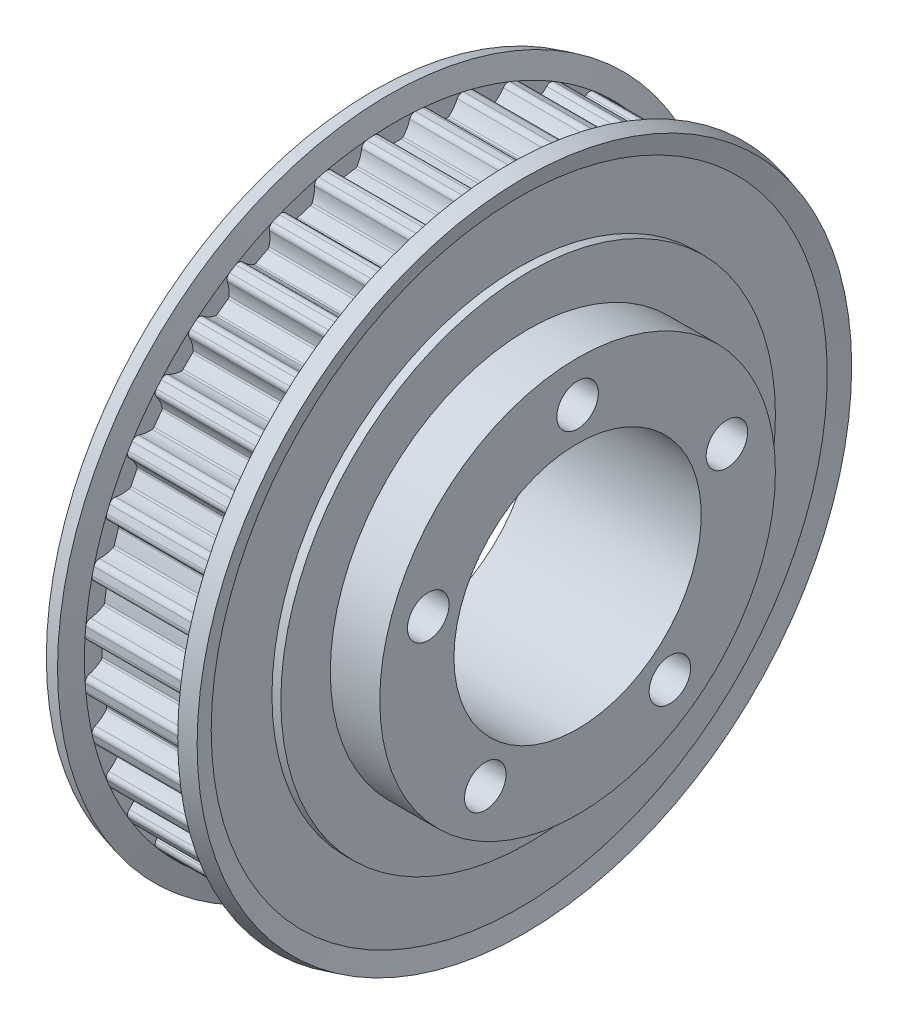
SolidWorks part; units mm, degrees
ref_plane "Front Plane" through (0, 0, 0) normal (0, 0, 1) x (1, 0, 0)
ref_plane "Top Plane" through (0, 0, 0) normal (0, 1, 0) x (1, 0, 0)
ref_plane "Right Plane" through (0, 0, 0) normal (1, 0, 0) x (0, 0, -1)
ref_plane "Plane1" through (0, 0, 0) normal (0, 0, 1) x (1, 0, 0)
sketch "Sketch1" plane through (0, 0, 0) normal (0, 0, 1) x (1, 0, 0)
  line L0 (0, 0) -> (0, 25)
  line L1 (0, 25) -> (0.9, 25)
  line L2 (0.9, 25) -> (0.9, 31.1394)
  line L3 (0.9, 31.1394) -> (0.3784, 33.0859)
  line L4 (0.3784, 33.0859) -> (1.9239, 33.5)
  line L5 (1.9239, 33.5) -> (2.5, 31.35)
  line L6 (2.5, 31.35) -> (13.5, 31.35)
  line L7 (13.5, 31.35) -> (14.0761, 33.5)
  line L8 (14.0761, 33.5) -> (15.6216, 33.0859)
  line L9 (15.6216, 33.0859) -> (15.1, 31.1394)
  line L10 (15.1, 31.1394) -> (15.1, 25)
  line L11 (15.1, 25) -> (16, 25)
  line L12 (16, 25) -> (16, 23.5)
  line L13 (16, 23.5) -> (21, 23.5)
  line L14 (21, 23.5) -> (21, 0)
  line L15 (21, 0) -> (0, 0)
  line L16 (21, 0) -> (0, 0) construction
revolve "Revolve1" add sketch "Sketch1" angle 360 about L16 reverse direction yes
ref_plane "Plane2" through (0, 0, 0) normal (0, 0, 1) x (1, 0, 0)
sketch "Sketch2" plane through (0, 0, 0) normal (0, 0, 1) x (1, 0, 0)
  line L0 (0, 0) -> (0, 12.5)
  line L1 (0, 12.5) -> (21, 12.5)
  line L2 (21, 12.5) -> (21, 0)
  line L3 (21, 0) -> (0, 0)
  line L4 (21, 0) -> (0, 0) construction
revolve "Cut-Revolve1" cut sketch "Sketch2" angle 360 about L4 reverse direction yes
ref_plane "Plane3" through (2.5, 0, 0) normal (1, 0, 0) x (0, 0, -1)
sketch "Sketch3" plane through (2.5, 0, 0) normal (1, 0, 0) x (0, 0, -1)
  line L0 (2.0877, 31.2804) -> (2.0877, 31.7615)
  line L1 (-2.0877, 31.7615) -> (-2.0877, 31.2804)
  arc A0 (-2.0877, 31.2804) -> (-1.5225, 30.8836) centre (-2.0511, 30.7316) cw
  arc A1 (-1.5225, 30.8836) -> (-0.8639, 29.6599) centre (1.625, 31.7885) ccw
  arc A2 (-0.8639, 29.6599) -> (-0.6683, 29.5725) centre (-0.6739, 29.8224) ccw
  arc A3 (-0.6683, 29.5725) -> (0.6683, 29.5725) centre (0, 0) cw
  arc A4 (0.6683, 29.5725) -> (0.8639, 29.6599) centre (0.6739, 29.8224) ccw
  arc A5 (0.8639, 29.6599) -> (1.5225, 30.8836) centre (-1.625, 31.7885) ccw
  arc A6 (1.5225, 30.8836) -> (2.0877, 31.2804) centre (2.0511, 30.7316) cw
  arc A7 (2.0877, 31.7615) -> (-2.0877, 31.7615) centre (0, 0) ccw
extrude "Cut-Extrude1" cut sketch "Sketch3" along normal blind 11
ref_plane "Plane4" through (2.5, 0, 0) normal (1, 0, 0) x (0, 0, -1)
sketch "Sketch4" plane through (2.5, 0, 0) normal (1, 0, 0) x (0, 0, -1)
  line L0 (6.9554, 30.5687) -> (7.0306, 31.0438)
  line L1 (2.9066, 31.697) -> (2.8313, 31.2219)
  arc A0 (2.8313, 31.2219) -> (3.3275, 30.7415) centre (2.7816, 30.6741) cw
  arc A1 (3.3275, 30.7415) -> (3.7865, 29.4299) centre (6.5778, 31.1429) ccw
  arc A2 (3.7865, 29.4299) -> (3.9661, 29.3129) centre (3.9996, 29.5606) ccw
  arc A3 (3.9661, 29.3129) -> (5.2862, 29.1038) centre (0, 0) cw
  arc A4 (5.2862, 29.1038) -> (5.4931, 29.1596) centre (5.3309, 29.3498) ccw
  arc A5 (5.4931, 29.1596) -> (6.335, 30.2652) centre (3.3678, 31.6513) ccw
  arc A6 (6.335, 30.2652) -> (6.9554, 30.5687) centre (6.8333, 30.0324) cw
  arc A7 (7.0306, 31.0438) -> (2.9066, 31.697) centre (0, 0) ccw
extrude "Cut-Extrude2" cut sketch "Sketch4" along normal blind 11
ref_plane "Plane5" through (2.5, 0, 0) normal (1, 0, 0) x (0, 0, -1)
sketch "Sketch5" plane through (2.5, 0, 0) normal (1, 0, 0) x (0, 0, -1)
  line L0 (11.6517, 29.1043) -> (11.8004, 29.5618)
  line L1 (7.8293, 30.8521) -> (7.6806, 30.3946)
  arc A0 (7.6806, 30.3946) -> (8.0956, 29.8425) centre (7.5459, 29.8613) cw
  arc A1 (8.0956, 29.8425) -> (8.3438, 28.4752) centre (11.3687, 29.7305) ccw
  arc A2 (8.3438, 28.4752) -> (8.5028, 28.3316) centre (8.5747, 28.571) ccw
  arc A3 (8.5028, 28.3316) -> (9.774, 27.9186) centre (0, 0) cw
  arc A4 (9.774, 27.9186) -> (9.987, 27.9413) centre (9.8566, 28.1545) ccw
  arc A5 (9.987, 27.9413) -> (10.9915, 28.9016) centre (8.2777, 30.7348) ccw
  arc A6 (10.9915, 28.9016) -> (11.6517, 29.1043) centre (11.4473, 28.5937) cw
  arc A7 (11.8004, 29.5618) -> (7.8293, 30.8521) centre (0, 0) ccw
extrude "Cut-Extrude3" cut sketch "Sketch5" along normal blind 11
ref_plane "Plane6" through (2.5, 0, 0) normal (1, 0, 0) x (0, 0, -1)
sketch "Sketch6" plane through (2.5, 0, 0) normal (1, 0, 0) x (0, 0, -1)
  line L0 (16.0612, 26.9232) -> (16.2796, 27.3519)
  line L1 (12.5592, 29.2475) -> (12.3408, 28.8189)
  arc A0 (12.3408, 28.8189) -> (12.6643, 28.2087) centre (12.1243, 28.3133) cw
  arc A1 (12.6643, 28.2087) -> (12.6956, 26.8194) centre (15.8796, 27.586) ccw
  arc A2 (12.6956, 26.8194) -> (12.8302, 26.6526) centre (12.9386, 26.8779) ccw
  arc A3 (12.8302, 26.6526) -> (14.021, 26.0459) centre (0, 0) cw
  arc A4 (14.021, 26.0459) -> (14.2351, 26.035) centre (14.1396, 26.266) ccw
  arc A5 (14.2351, 26.035) -> (15.3774, 26.8263) centre (12.9838, 29.0615) ccw
  arc A6 (15.3774, 26.8263) -> (16.0612, 26.9232) centre (15.7794, 26.4509) cw
  arc A7 (16.2796, 27.3519) -> (12.5592, 29.2475) centre (0, 0) ccw
extrude "Cut-Extrude4" cut sketch "Sketch6" along normal blind 11
ref_plane "Plane7" through (2.5, 0, 0) normal (1, 0, 0) x (0, 0, -1)
sketch "Sketch7" plane through (2.5, 0, 0) normal (1, 0, 0) x (0, 0, -1)
  line L0 (20.0752, 24.0793) -> (20.3579, 24.4684)
  line L1 (16.9799, 26.9227) -> (16.6972, 26.5335)
  arc A0 (16.6972, 26.5335) -> (16.9212, 25.8803) centre (16.4042, 26.068) cw
  arc A1 (16.9212, 25.8803) -> (16.7347, 24.5032) centre (19.9995, 24.7623) ccw
  arc A2 (16.7347, 24.5032) -> (16.8416, 24.3174) centre (16.9839, 24.5229) ccw
  arc A3 (16.8416, 24.3174) -> (17.9229, 23.5318) centre (0, 0) cw
  arc A4 (17.9229, 23.5318) -> (18.1326, 23.4876) centre (18.0744, 23.7307) ccw
  arc A5 (18.1326, 23.4876) -> (19.3847, 24.0904) centre (17.3702, 26.6726) ccw
  arc A6 (19.3847, 24.0904) -> (20.0752, 24.0793) centre (19.723, 23.6568) cw
  arc A7 (20.3579, 24.4684) -> (16.9799, 26.9227) centre (0, 0) ccw
extrude "Cut-Extrude5" cut sketch "Sketch7" along normal blind 11
ref_plane "Plane8" through (2.5, 0, 0) normal (1, 0, 0) x (0, 0, -1)
sketch "Sketch8" plane through (2.5, 0, 0) normal (1, 0, 0) x (0, 0, -1)
  line L0 (23.5948, 20.6423) -> (23.935, 20.9825)
  line L1 (20.9825, 23.935) -> (20.6423, 23.5948)
  arc A0 (20.6423, 23.5948) -> (20.7614, 22.9146) centre (20.2802, 23.1809) cw
  arc A1 (20.7614, 22.9146) -> (20.3618, 21.5836) centre (23.6269, 21.3288) ccw
  arc A2 (20.3618, 21.5836) -> (20.4383, 21.3834) centre (20.6111, 21.5641) ccw
  arc A3 (20.4383, 21.3834) -> (21.3834, 20.4383) centre (0, 0) cw
  arc A4 (21.3834, 20.4383) -> (21.5836, 20.3618) centre (21.5641, 20.6111) ccw
  arc A5 (21.5836, 20.3618) -> (22.9146, 20.7614) centre (21.3288, 23.6269) ccw
  arc A6 (22.9146, 20.7614) -> (23.5948, 20.6423) centre (23.1809, 20.2802) cw
  arc A7 (23.935, 20.9825) -> (20.9825, 23.935) centre (0, 0) ccw
extrude "Cut-Extrude6" cut sketch "Sketch8" along normal blind 11
ref_plane "Plane9" through (2.5, 0, 0) normal (1, 0, 0) x (0, 0, -1)
sketch "Sketch9" plane through (2.5, 0, 0) normal (1, 0, 0) x (0, 0, -1)
  line L0 (26.5335, 16.6972) -> (26.9227, 16.9799)
  line L1 (24.4684, 20.3579) -> (24.0793, 20.0752)
  arc A0 (24.0793, 20.0752) -> (24.0904, 19.3847) centre (23.6568, 19.723) cw
  arc A1 (24.0904, 19.3847) -> (23.4876, 18.1326) centre (26.6726, 17.3702) ccw
  arc A2 (23.4876, 18.1326) -> (23.5318, 17.9229) centre (23.7307, 18.0744) ccw
  arc A3 (23.5318, 17.9229) -> (24.3174, 16.8416) centre (0, 0) cw
  arc A4 (24.3174, 16.8416) -> (24.5032, 16.7347) centre (24.5229, 16.9839) ccw
  arc A5 (24.5032, 16.7347) -> (25.8803, 16.9212) centre (24.7623, 19.9995) ccw
  arc A6 (25.8803, 16.9212) -> (26.5335, 16.6972) centre (26.068, 16.4042) cw
  arc A7 (26.9227, 16.9799) -> (24.4684, 20.3579) centre (0, 0) ccw
extrude "Cut-Extrude7" cut sketch "Sketch9" along normal blind 11
ref_plane "Plane10" through (2.5, 0, 0) normal (1, 0, 0) x (0, 0, -1)
sketch "Sketch10" plane through (2.5, 0, 0) normal (1, 0, 0) x (0, 0, -1)
  line L0 (28.8189, 12.3408) -> (29.2475, 12.5592)
  line L1 (27.3519, 16.2796) -> (26.9232, 16.0612)
  arc A0 (26.9232, 16.0612) -> (26.8263, 15.3774) centre (26.4509, 15.7794) cw
  arc A1 (26.8263, 15.3774) -> (26.035, 14.2351) centre (29.0615, 12.9838) ccw
  arc A2 (26.035, 14.2351) -> (26.0459, 14.021) centre (26.266, 14.1396) ccw
  arc A3 (26.0459, 14.021) -> (26.6526, 12.8302) centre (0, 0) cw
  arc A4 (26.6526, 12.8302) -> (26.8194, 12.6956) centre (26.8779, 12.9386) ccw
  arc A5 (26.8194, 12.6956) -> (28.2087, 12.6643) centre (27.586, 15.8796) ccw
  arc A6 (28.2087, 12.6643) -> (28.8189, 12.3408) centre (28.3133, 12.1243) cw
  arc A7 (29.2475, 12.5592) -> (27.3519, 16.2796) centre (0, 0) ccw
extrude "Cut-Extrude8" cut sketch "Sketch10" along normal blind 11
ref_plane "Plane11" through (2.5, 0, 0) normal (1, 0, 0) x (0, 0, -1)
sketch "Sketch11" plane through (2.5, 0, 0) normal (1, 0, 0) x (0, 0, -1)
  line L0 (30.3946, 7.6806) -> (30.8521, 7.8293)
  line L1 (29.5618, 11.8004) -> (29.1043, 11.6517)
  arc A0 (29.1043, 11.6517) -> (28.9016, 10.9915) centre (28.5937, 11.4473) cw
  arc A1 (28.9016, 10.9915) -> (27.9413, 9.987) centre (30.7348, 8.2777) ccw
  arc A2 (27.9413, 9.987) -> (27.9186, 9.774) centre (28.1545, 9.8566) ccw
  arc A3 (27.9186, 9.774) -> (28.3316, 8.5028) centre (0, 0) cw
  arc A4 (28.3316, 8.5028) -> (28.4752, 8.3438) centre (28.571, 8.5747) ccw
  arc A5 (28.4752, 8.3438) -> (29.8425, 8.0956) centre (29.7305, 11.3687) ccw
  arc A6 (29.8425, 8.0956) -> (30.3946, 7.6806) centre (29.8613, 7.5459) cw
  arc A7 (30.8521, 7.8293) -> (29.5618, 11.8004) centre (0, 0) ccw
extrude "Cut-Extrude9" cut sketch "Sketch11" along normal blind 11
ref_plane "Plane12" through (2.5, 0, 0) normal (1, 0, 0) x (0, 0, -1)
sketch "Sketch12" plane through (2.5, 0, 0) normal (1, 0, 0) x (0, 0, -1)
  line L0 (31.2219, 2.8313) -> (31.697, 2.9066)
  line L1 (31.0438, 7.0306) -> (30.5687, 6.9554)
  arc A0 (30.5687, 6.9554) -> (30.2652, 6.335) centre (30.0324, 6.8333) cw
  arc A1 (30.2652, 6.335) -> (29.1596, 5.4931) centre (31.6513, 3.3678) ccw
  arc A2 (29.1596, 5.4931) -> (29.1038, 5.2862) centre (29.3498, 5.3309) ccw
  arc A3 (29.1038, 5.2862) -> (29.3129, 3.9661) centre (0, 0) cw
  arc A4 (29.3129, 3.9661) -> (29.4299, 3.7865) centre (29.5606, 3.9996) ccw
  arc A5 (29.4299, 3.7865) -> (30.7415, 3.3275) centre (31.1429, 6.5778) ccw
  arc A6 (30.7415, 3.3275) -> (31.2219, 2.8313) centre (30.6741, 2.7816) cw
  arc A7 (31.697, 2.9066) -> (31.0438, 7.0306) centre (0, 0) ccw
extrude "Cut-Extrude10" cut sketch "Sketch12" along normal blind 11
ref_plane "Plane13" through (2.5, 0, 0) normal (1, 0, 0) x (0, 0, -1)
sketch "Sketch13" plane through (2.5, 0, 0) normal (1, 0, 0) x (0, 0, -1)
  line L0 (31.2804, -2.0877) -> (31.7615, -2.0877)
  line L1 (31.7615, 2.0877) -> (31.2804, 2.0877)
  arc A0 (31.2804, 2.0877) -> (30.8836, 1.5225) centre (30.7316, 2.0511) cw
  arc A1 (30.8836, 1.5225) -> (29.6599, 0.8639) centre (31.7885, -1.625) ccw
  arc A2 (29.6599, 0.8639) -> (29.5725, 0.6683) centre (29.8224, 0.6739) ccw
  arc A3 (29.5725, 0.6683) -> (29.5725, -0.6683) centre (0, 0) cw
  arc A4 (29.5725, -0.6683) -> (29.6599, -0.8639) centre (29.8224, -0.6739) ccw
  arc A5 (29.6599, -0.8639) -> (30.8836, -1.5225) centre (31.7885, 1.625) ccw
  arc A6 (30.8836, -1.5225) -> (31.2804, -2.0877) centre (30.7316, -2.0511) cw
  arc A7 (31.7615, -2.0877) -> (31.7615, 2.0877) centre (0, 0) ccw
extrude "Cut-Extrude11" cut sketch "Sketch13" along normal blind 11
ref_plane "Plane14" through (2.5, 0, 0) normal (1, 0, 0) x (0, 0, -1)
sketch "Sketch14" plane through (2.5, 0, 0) normal (1, 0, 0) x (0, 0, -1)
  line L0 (30.5687, -6.9554) -> (31.0438, -7.0306)
  line L1 (31.697, -2.9066) -> (31.2219, -2.8313)
  arc A0 (31.2219, -2.8313) -> (30.7415, -3.3275) centre (30.6741, -2.7816) cw
  arc A1 (30.7415, -3.3275) -> (29.4299, -3.7865) centre (31.1429, -6.5778) ccw
  arc A2 (29.4299, -3.7865) -> (29.3129, -3.9661) centre (29.5606, -3.9996) ccw
  arc A3 (29.3129, -3.9661) -> (29.1038, -5.2862) centre (0, 0) cw
  arc A4 (29.1038, -5.2862) -> (29.1596, -5.4931) centre (29.3498, -5.3309) ccw
  arc A5 (29.1596, -5.4931) -> (30.2652, -6.335) centre (31.6513, -3.3678) ccw
  arc A6 (30.2652, -6.335) -> (30.5687, -6.9554) centre (30.0324, -6.8333) cw
  arc A7 (31.0438, -7.0306) -> (31.697, -2.9066) centre (0, 0) ccw
extrude "Cut-Extrude12" cut sketch "Sketch14" along normal blind 11
ref_plane "Plane15" through (2.5, 0, 0) normal (1, 0, 0) x (0, 0, -1)
sketch "Sketch15" plane through (2.5, 0, 0) normal (1, 0, 0) x (0, 0, -1)
  line L0 (29.1043, -11.6517) -> (29.5618, -11.8004)
  line L1 (30.8521, -7.8293) -> (30.3946, -7.6806)
  arc A0 (30.3946, -7.6806) -> (29.8425, -8.0956) centre (29.8613, -7.5459) cw
  arc A1 (29.8425, -8.0956) -> (28.4752, -8.3438) centre (29.7305, -11.3687) ccw
  arc A2 (28.4752, -8.3438) -> (28.3316, -8.5028) centre (28.571, -8.5747) ccw
  arc A3 (28.3316, -8.5028) -> (27.9186, -9.774) centre (0, 0) cw
  arc A4 (27.9186, -9.774) -> (27.9413, -9.987) centre (28.1545, -9.8566) ccw
  arc A5 (27.9413, -9.987) -> (28.9016, -10.9915) centre (30.7348, -8.2777) ccw
  arc A6 (28.9016, -10.9915) -> (29.1043, -11.6517) centre (28.5937, -11.4473) cw
  arc A7 (29.5618, -11.8004) -> (30.8521, -7.8293) centre (0, 0) ccw
extrude "Cut-Extrude13" cut sketch "Sketch15" along normal blind 11
ref_plane "Plane16" through (2.5, 0, 0) normal (1, 0, 0) x (0, 0, -1)
sketch "Sketch16" plane through (2.5, 0, 0) normal (1, 0, 0) x (0, 0, -1)
  line L0 (26.9232, -16.0612) -> (27.3519, -16.2796)
  line L1 (29.2475, -12.5592) -> (28.8189, -12.3408)
  arc A0 (28.8189, -12.3408) -> (28.2087, -12.6643) centre (28.3133, -12.1243) cw
  arc A1 (28.2087, -12.6643) -> (26.8194, -12.6956) centre (27.586, -15.8796) ccw
  arc A2 (26.8194, -12.6956) -> (26.6526, -12.8302) centre (26.8779, -12.9386) ccw
  arc A3 (26.6526, -12.8302) -> (26.0459, -14.021) centre (0, 0) cw
  arc A4 (26.0459, -14.021) -> (26.035, -14.2351) centre (26.266, -14.1396) ccw
  arc A5 (26.035, -14.2351) -> (26.8263, -15.3774) centre (29.0615, -12.9838) ccw
  arc A6 (26.8263, -15.3774) -> (26.9232, -16.0612) centre (26.4509, -15.7794) cw
  arc A7 (27.3519, -16.2796) -> (29.2475, -12.5592) centre (0, 0) ccw
extrude "Cut-Extrude14" cut sketch "Sketch16" along normal blind 11
ref_plane "Plane17" through (2.5, 0, 0) normal (1, 0, 0) x (0, 0, -1)
sketch "Sketch17" plane through (2.5, 0, 0) normal (1, 0, 0) x (0, 0, -1)
  line L0 (24.0793, -20.0752) -> (24.4684, -20.3579)
  line L1 (26.9227, -16.9799) -> (26.5335, -16.6972)
  arc A0 (26.5335, -16.6972) -> (25.8803, -16.9212) centre (26.068, -16.4042) cw
  arc A1 (25.8803, -16.9212) -> (24.5032, -16.7347) centre (24.7623, -19.9995) ccw
  arc A2 (24.5032, -16.7347) -> (24.3174, -16.8416) centre (24.5229, -16.9839) ccw
  arc A3 (24.3174, -16.8416) -> (23.5318, -17.9229) centre (0, 0) cw
  arc A4 (23.5318, -17.9229) -> (23.4876, -18.1326) centre (23.7307, -18.0744) ccw
  arc A5 (23.4876, -18.1326) -> (24.0904, -19.3847) centre (26.6726, -17.3702) ccw
  arc A6 (24.0904, -19.3847) -> (24.0793, -20.0752) centre (23.6568, -19.723) cw
  arc A7 (24.4684, -20.3579) -> (26.9227, -16.9799) centre (0, 0) ccw
extrude "Cut-Extrude15" cut sketch "Sketch17" along normal blind 11
ref_plane "Plane18" through (2.5, 0, 0) normal (1, 0, 0) x (0, 0, -1)
sketch "Sketch18" plane through (2.5, 0, 0) normal (1, 0, 0) x (0, 0, -1)
  line L0 (20.6423, -23.5948) -> (20.9825, -23.935)
  line L1 (23.935, -20.9825) -> (23.5948, -20.6423)
  arc A0 (23.5948, -20.6423) -> (22.9146, -20.7614) centre (23.1809, -20.2802) cw
  arc A1 (22.9146, -20.7614) -> (21.5836, -20.3618) centre (21.3288, -23.6269) ccw
  arc A2 (21.5836, -20.3618) -> (21.3834, -20.4383) centre (21.5641, -20.6111) ccw
  arc A3 (21.3834, -20.4383) -> (20.4383, -21.3834) centre (0, 0) cw
  arc A4 (20.4383, -21.3834) -> (20.3618, -21.5836) centre (20.6111, -21.5641) ccw
  arc A5 (20.3618, -21.5836) -> (20.7614, -22.9146) centre (23.6269, -21.3288) ccw
  arc A6 (20.7614, -22.9146) -> (20.6423, -23.5948) centre (20.2802, -23.1809) cw
  arc A7 (20.9825, -23.935) -> (23.935, -20.9825) centre (0, 0) ccw
extrude "Cut-Extrude16" cut sketch "Sketch18" along normal blind 11
ref_plane "Plane19" through (2.5, 0, 0) normal (1, 0, 0) x (0, 0, -1)
sketch "Sketch19" plane through (2.5, 0, 0) normal (1, 0, 0) x (0, 0, -1)
  line L0 (16.6972, -26.5335) -> (16.9799, -26.9227)
  line L1 (20.3579, -24.4684) -> (20.0752, -24.0793)
  arc A0 (20.0752, -24.0793) -> (19.3847, -24.0904) centre (19.723, -23.6568) cw
  arc A1 (19.3847, -24.0904) -> (18.1326, -23.4876) centre (17.3702, -26.6726) ccw
  arc A2 (18.1326, -23.4876) -> (17.9229, -23.5318) centre (18.0744, -23.7307) ccw
  arc A3 (17.9229, -23.5318) -> (16.8416, -24.3174) centre (0, 0) cw
  arc A4 (16.8416, -24.3174) -> (16.7347, -24.5032) centre (16.9839, -24.5229) ccw
  arc A5 (16.7347, -24.5032) -> (16.9212, -25.8803) centre (19.9995, -24.7623) ccw
  arc A6 (16.9212, -25.8803) -> (16.6972, -26.5335) centre (16.4042, -26.068) cw
  arc A7 (16.9799, -26.9227) -> (20.3579, -24.4684) centre (0, 0) ccw
extrude "Cut-Extrude17" cut sketch "Sketch19" along normal blind 11
ref_plane "Plane20" through (2.5, 0, 0) normal (1, 0, 0) x (0, 0, -1)
sketch "Sketch20" plane through (2.5, 0, 0) normal (1, 0, 0) x (0, 0, -1)
  line L0 (12.3408, -28.8189) -> (12.5592, -29.2475)
  line L1 (16.2796, -27.3519) -> (16.0612, -26.9232)
  arc A0 (16.0612, -26.9232) -> (15.3774, -26.8263) centre (15.7794, -26.4509) cw
  arc A1 (15.3774, -26.8263) -> (14.2351, -26.035) centre (12.9838, -29.0615) ccw
  arc A2 (14.2351, -26.035) -> (14.021, -26.0459) centre (14.1396, -26.266) ccw
  arc A3 (14.021, -26.0459) -> (12.8302, -26.6526) centre (0, 0) cw
  arc A4 (12.8302, -26.6526) -> (12.6956, -26.8194) centre (12.9386, -26.8779) ccw
  arc A5 (12.6956, -26.8194) -> (12.6643, -28.2087) centre (15.8796, -27.586) ccw
  arc A6 (12.6643, -28.2087) -> (12.3408, -28.8189) centre (12.1243, -28.3133) cw
  arc A7 (12.5592, -29.2475) -> (16.2796, -27.3519) centre (0, 0) ccw
extrude "Cut-Extrude18" cut sketch "Sketch20" along normal blind 11
ref_plane "Plane21" through (2.5, 0, 0) normal (1, 0, 0) x (0, 0, -1)
sketch "Sketch21" plane through (2.5, 0, 0) normal (1, 0, 0) x (0, 0, -1)
  line L0 (7.6806, -30.3946) -> (7.8293, -30.8521)
  line L1 (11.8004, -29.5618) -> (11.6517, -29.1043)
  arc A0 (11.6517, -29.1043) -> (10.9915, -28.9016) centre (11.4473, -28.5937) cw
  arc A1 (10.9915, -28.9016) -> (9.987, -27.9413) centre (8.2777, -30.7348) ccw
  arc A2 (9.987, -27.9413) -> (9.774, -27.9186) centre (9.8566, -28.1545) ccw
  arc A3 (9.774, -27.9186) -> (8.5028, -28.3316) centre (0, 0) cw
  arc A4 (8.5028, -28.3316) -> (8.3438, -28.4752) centre (8.5747, -28.571) ccw
  arc A5 (8.3438, -28.4752) -> (8.0956, -29.8425) centre (11.3687, -29.7305) ccw
  arc A6 (8.0956, -29.8425) -> (7.6806, -30.3946) centre (7.5459, -29.8613) cw
  arc A7 (7.8293, -30.8521) -> (11.8004, -29.5618) centre (0, 0) ccw
extrude "Cut-Extrude19" cut sketch "Sketch21" along normal blind 11
ref_plane "Plane22" through (2.5, 0, 0) normal (1, 0, 0) x (0, 0, -1)
sketch "Sketch22" plane through (2.5, 0, 0) normal (1, 0, 0) x (0, 0, -1)
  line L0 (2.8313, -31.2219) -> (2.9066, -31.697)
  line L1 (7.0306, -31.0438) -> (6.9554, -30.5687)
  arc A0 (6.9554, -30.5687) -> (6.335, -30.2652) centre (6.8333, -30.0324) cw
  arc A1 (6.335, -30.2652) -> (5.4931, -29.1596) centre (3.3678, -31.6513) ccw
  arc A2 (5.4931, -29.1596) -> (5.2862, -29.1038) centre (5.3309, -29.3498) ccw
  arc A3 (5.2862, -29.1038) -> (3.9661, -29.3129) centre (0, 0) cw
  arc A4 (3.9661, -29.3129) -> (3.7865, -29.4299) centre (3.9996, -29.5606) ccw
  arc A5 (3.7865, -29.4299) -> (3.3275, -30.7415) centre (6.5778, -31.1429) ccw
  arc A6 (3.3275, -30.7415) -> (2.8313, -31.2219) centre (2.7816, -30.6741) cw
  arc A7 (2.9066, -31.697) -> (7.0306, -31.0438) centre (0, 0) ccw
extrude "Cut-Extrude20" cut sketch "Sketch22" along normal blind 11
ref_plane "Plane23" through (2.5, 0, 0) normal (1, 0, 0) x (0, 0, -1)
sketch "Sketch23" plane through (2.5, 0, 0) normal (1, 0, 0) x (0, 0, -1)
  line L0 (-2.0877, -31.2804) -> (-2.0877, -31.7615)
  line L1 (2.0877, -31.7615) -> (2.0877, -31.2804)
  arc A0 (2.0877, -31.2804) -> (1.5225, -30.8836) centre (2.0511, -30.7316) cw
  arc A1 (1.5225, -30.8836) -> (0.8639, -29.6599) centre (-1.625, -31.7885) ccw
  arc A2 (0.8639, -29.6599) -> (0.6683, -29.5725) centre (0.6739, -29.8224) ccw
  arc A3 (0.6683, -29.5725) -> (-0.6683, -29.5725) centre (0, 0) cw
  arc A4 (-0.6683, -29.5725) -> (-0.8639, -29.6599) centre (-0.6739, -29.8224) ccw
  arc A5 (-0.8639, -29.6599) -> (-1.5225, -30.8836) centre (1.625, -31.7885) ccw
  arc A6 (-1.5225, -30.8836) -> (-2.0877, -31.2804) centre (-2.0511, -30.7316) cw
  arc A7 (-2.0877, -31.7615) -> (2.0877, -31.7615) centre (0, 0) ccw
extrude "Cut-Extrude21" cut sketch "Sketch23" along normal blind 11
ref_plane "Plane24" through (2.5, 0, 0) normal (1, 0, 0) x (0, 0, -1)
sketch "Sketch24" plane through (2.5, 0, 0) normal (1, 0, 0) x (0, 0, -1)
  line L0 (-6.9554, -30.5687) -> (-7.0306, -31.0438)
  line L1 (-2.9066, -31.697) -> (-2.8313, -31.2219)
  arc A0 (-2.8313, -31.2219) -> (-3.3275, -30.7415) centre (-2.7816, -30.6741) cw
  arc A1 (-3.3275, -30.7415) -> (-3.7865, -29.4299) centre (-6.5778, -31.1429) ccw
  arc A2 (-3.7865, -29.4299) -> (-3.9661, -29.3129) centre (-3.9996, -29.5606) ccw
  arc A3 (-3.9661, -29.3129) -> (-5.2862, -29.1038) centre (0, 0) cw
  arc A4 (-5.2862, -29.1038) -> (-5.4931, -29.1596) centre (-5.3309, -29.3498) ccw
  arc A5 (-5.4931, -29.1596) -> (-6.335, -30.2652) centre (-3.3678, -31.6513) ccw
  arc A6 (-6.335, -30.2652) -> (-6.9554, -30.5687) centre (-6.8333, -30.0324) cw
  arc A7 (-7.0306, -31.0438) -> (-2.9066, -31.697) centre (0, 0) ccw
extrude "Cut-Extrude22" cut sketch "Sketch24" along normal blind 11
ref_plane "Plane25" through (2.5, 0, 0) normal (1, 0, 0) x (0, 0, -1)
sketch "Sketch25" plane through (2.5, 0, 0) normal (1, 0, 0) x (0, 0, -1)
  line L0 (-11.6517, -29.1043) -> (-11.8004, -29.5618)
  line L1 (-7.8293, -30.8521) -> (-7.6806, -30.3946)
  arc A0 (-7.6806, -30.3946) -> (-8.0956, -29.8425) centre (-7.5459, -29.8613) cw
  arc A1 (-8.0956, -29.8425) -> (-8.3438, -28.4752) centre (-11.3687, -29.7305) ccw
  arc A2 (-8.3438, -28.4752) -> (-8.5028, -28.3316) centre (-8.5747, -28.571) ccw
  arc A3 (-8.5028, -28.3316) -> (-9.774, -27.9186) centre (0, 0) cw
  arc A4 (-9.774, -27.9186) -> (-9.987, -27.9413) centre (-9.8566, -28.1545) ccw
  arc A5 (-9.987, -27.9413) -> (-10.9915, -28.9016) centre (-8.2777, -30.7348) ccw
  arc A6 (-10.9915, -28.9016) -> (-11.6517, -29.1043) centre (-11.4473, -28.5937) cw
  arc A7 (-11.8004, -29.5618) -> (-7.8293, -30.8521) centre (0, 0) ccw
extrude "Cut-Extrude23" cut sketch "Sketch25" along normal blind 11
ref_plane "Plane26" through (2.5, 0, 0) normal (1, 0, 0) x (0, 0, -1)
sketch "Sketch26" plane through (2.5, 0, 0) normal (1, 0, 0) x (0, 0, -1)
  line L0 (-16.0612, -26.9232) -> (-16.2796, -27.3519)
  line L1 (-12.5592, -29.2475) -> (-12.3408, -28.8189)
  arc A0 (-12.3408, -28.8189) -> (-12.6643, -28.2087) centre (-12.1243, -28.3133) cw
  arc A1 (-12.6643, -28.2087) -> (-12.6956, -26.8194) centre (-15.8796, -27.586) ccw
  arc A2 (-12.6956, -26.8194) -> (-12.8302, -26.6526) centre (-12.9386, -26.8779) ccw
  arc A3 (-12.8302, -26.6526) -> (-14.021, -26.0459) centre (0, 0) cw
  arc A4 (-14.021, -26.0459) -> (-14.2351, -26.035) centre (-14.1396, -26.266) ccw
  arc A5 (-14.2351, -26.035) -> (-15.3774, -26.8263) centre (-12.9838, -29.0615) ccw
  arc A6 (-15.3774, -26.8263) -> (-16.0612, -26.9232) centre (-15.7794, -26.4509) cw
  arc A7 (-16.2796, -27.3519) -> (-12.5592, -29.2475) centre (0, 0) ccw
extrude "Cut-Extrude24" cut sketch "Sketch26" along normal blind 11
ref_plane "Plane27" through (2.5, 0, 0) normal (1, 0, 0) x (0, 0, -1)
sketch "Sketch27" plane through (2.5, 0, 0) normal (1, 0, 0) x (0, 0, -1)
  line L0 (-20.0752, -24.0793) -> (-20.3579, -24.4684)
  line L1 (-16.9799, -26.9227) -> (-16.6972, -26.5335)
  arc A0 (-16.6972, -26.5335) -> (-16.9212, -25.8803) centre (-16.4042, -26.068) cw
  arc A1 (-16.9212, -25.8803) -> (-16.7347, -24.5032) centre (-19.9995, -24.7623) ccw
  arc A2 (-16.7347, -24.5032) -> (-16.8416, -24.3174) centre (-16.9839, -24.5229) ccw
  arc A3 (-16.8416, -24.3174) -> (-17.9229, -23.5318) centre (0, 0) cw
  arc A4 (-17.9229, -23.5318) -> (-18.1326, -23.4876) centre (-18.0744, -23.7307) ccw
  arc A5 (-18.1326, -23.4876) -> (-19.3847, -24.0904) centre (-17.3702, -26.6726) ccw
  arc A6 (-19.3847, -24.0904) -> (-20.0752, -24.0793) centre (-19.723, -23.6568) cw
  arc A7 (-20.3579, -24.4684) -> (-16.9799, -26.9227) centre (0, 0) ccw
extrude "Cut-Extrude25" cut sketch "Sketch27" along normal blind 11
ref_plane "Plane28" through (2.5, 0, 0) normal (1, 0, 0) x (0, 0, -1)
sketch "Sketch28" plane through (2.5, 0, 0) normal (1, 0, 0) x (0, 0, -1)
  line L0 (-23.5948, -20.6423) -> (-23.935, -20.9825)
  line L1 (-20.9825, -23.935) -> (-20.6423, -23.5948)
  arc A0 (-20.6423, -23.5948) -> (-20.7614, -22.9146) centre (-20.2802, -23.1809) cw
  arc A1 (-20.7614, -22.9146) -> (-20.3618, -21.5836) centre (-23.6269, -21.3288) ccw
  arc A2 (-20.3618, -21.5836) -> (-20.4383, -21.3834) centre (-20.6111, -21.5641) ccw
  arc A3 (-20.4383, -21.3834) -> (-21.3834, -20.4383) centre (0, 0) cw
  arc A4 (-21.3834, -20.4383) -> (-21.5836, -20.3618) centre (-21.5641, -20.6111) ccw
  arc A5 (-21.5836, -20.3618) -> (-22.9146, -20.7614) centre (-21.3288, -23.6269) ccw
  arc A6 (-22.9146, -20.7614) -> (-23.5948, -20.6423) centre (-23.1809, -20.2802) cw
  arc A7 (-23.935, -20.9825) -> (-20.9825, -23.935) centre (0, 0) ccw
extrude "Cut-Extrude26" cut sketch "Sketch28" along normal blind 11
ref_plane "Plane29" through (2.5, 0, 0) normal (1, 0, 0) x (0, 0, -1)
sketch "Sketch29" plane through (2.5, 0, 0) normal (1, 0, 0) x (0, 0, -1)
  line L0 (-26.5335, -16.6972) -> (-26.9227, -16.9799)
  line L1 (-24.4684, -20.3579) -> (-24.0793, -20.0752)
  arc A0 (-24.0793, -20.0752) -> (-24.0904, -19.3847) centre (-23.6568, -19.723) cw
  arc A1 (-24.0904, -19.3847) -> (-23.4876, -18.1326) centre (-26.6726, -17.3702) ccw
  arc A2 (-23.4876, -18.1326) -> (-23.5318, -17.9229) centre (-23.7307, -18.0744) ccw
  arc A3 (-23.5318, -17.9229) -> (-24.3174, -16.8416) centre (0, 0) cw
  arc A4 (-24.3174, -16.8416) -> (-24.5032, -16.7347) centre (-24.5229, -16.9839) ccw
  arc A5 (-24.5032, -16.7347) -> (-25.8803, -16.9212) centre (-24.7623, -19.9995) ccw
  arc A6 (-25.8803, -16.9212) -> (-26.5335, -16.6972) centre (-26.068, -16.4042) cw
  arc A7 (-26.9227, -16.9799) -> (-24.4684, -20.3579) centre (0, 0) ccw
extrude "Cut-Extrude27" cut sketch "Sketch29" along normal blind 11
ref_plane "Plane30" through (2.5, 0, 0) normal (1, 0, 0) x (0, 0, -1)
sketch "Sketch30" plane through (2.5, 0, 0) normal (1, 0, 0) x (0, 0, -1)
  line L0 (-28.8189, -12.3408) -> (-29.2475, -12.5592)
  line L1 (-27.3519, -16.2796) -> (-26.9232, -16.0612)
  arc A0 (-26.9232, -16.0612) -> (-26.8263, -15.3774) centre (-26.4509, -15.7794) cw
  arc A1 (-26.8263, -15.3774) -> (-26.035, -14.2351) centre (-29.0615, -12.9838) ccw
  arc A2 (-26.035, -14.2351) -> (-26.0459, -14.021) centre (-26.266, -14.1396) ccw
  arc A3 (-26.0459, -14.021) -> (-26.6526, -12.8302) centre (0, 0) cw
  arc A4 (-26.6526, -12.8302) -> (-26.8194, -12.6956) centre (-26.8779, -12.9386) ccw
  arc A5 (-26.8194, -12.6956) -> (-28.2087, -12.6643) centre (-27.586, -15.8796) ccw
  arc A6 (-28.2087, -12.6643) -> (-28.8189, -12.3408) centre (-28.3133, -12.1243) cw
  arc A7 (-29.2475, -12.5592) -> (-27.3519, -16.2796) centre (0, 0) ccw
extrude "Cut-Extrude28" cut sketch "Sketch30" along normal blind 11
ref_plane "Plane31" through (2.5, 0, 0) normal (1, 0, 0) x (0, 0, -1)
sketch "Sketch31" plane through (2.5, 0, 0) normal (1, 0, 0) x (0, 0, -1)
  line L0 (-30.3946, -7.6806) -> (-30.8521, -7.8293)
  line L1 (-29.5618, -11.8004) -> (-29.1043, -11.6517)
  arc A0 (-29.1043, -11.6517) -> (-28.9016, -10.9915) centre (-28.5937, -11.4473) cw
  arc A1 (-28.9016, -10.9915) -> (-27.9413, -9.987) centre (-30.7348, -8.2777) ccw
  arc A2 (-27.9413, -9.987) -> (-27.9186, -9.774) centre (-28.1545, -9.8566) ccw
  arc A3 (-27.9186, -9.774) -> (-28.3316, -8.5028) centre (0, 0) cw
  arc A4 (-28.3316, -8.5028) -> (-28.4752, -8.3438) centre (-28.571, -8.5747) ccw
  arc A5 (-28.4752, -8.3438) -> (-29.8425, -8.0956) centre (-29.7305, -11.3687) ccw
  arc A6 (-29.8425, -8.0956) -> (-30.3946, -7.6806) centre (-29.8613, -7.5459) cw
  arc A7 (-30.8521, -7.8293) -> (-29.5618, -11.8004) centre (0, 0) ccw
extrude "Cut-Extrude29" cut sketch "Sketch31" along normal blind 11
ref_plane "Plane32" through (2.5, 0, 0) normal (1, 0, 0) x (0, 0, -1)
sketch "Sketch32" plane through (2.5, 0, 0) normal (1, 0, 0) x (0, 0, -1)
  line L0 (-31.2219, -2.8313) -> (-31.697, -2.9066)
  line L1 (-31.0438, -7.0306) -> (-30.5687, -6.9554)
  arc A0 (-30.5687, -6.9554) -> (-30.2652, -6.335) centre (-30.0324, -6.8333) cw
  arc A1 (-30.2652, -6.335) -> (-29.1596, -5.4931) centre (-31.6513, -3.3678) ccw
  arc A2 (-29.1596, -5.4931) -> (-29.1038, -5.2862) centre (-29.3498, -5.3309) ccw
  arc A3 (-29.1038, -5.2862) -> (-29.3129, -3.9661) centre (0, 0) cw
  arc A4 (-29.3129, -3.9661) -> (-29.4299, -3.7865) centre (-29.5606, -3.9996) ccw
  arc A5 (-29.4299, -3.7865) -> (-30.7415, -3.3275) centre (-31.1429, -6.5778) ccw
  arc A6 (-30.7415, -3.3275) -> (-31.2219, -2.8313) centre (-30.6741, -2.7816) cw
  arc A7 (-31.697, -2.9066) -> (-31.0438, -7.0306) centre (0, 0) ccw
extrude "Cut-Extrude30" cut sketch "Sketch32" along normal blind 11
ref_plane "Plane33" through (2.5, 0, 0) normal (1, 0, 0) x (0, 0, -1)
sketch "Sketch33" plane through (2.5, 0, 0) normal (1, 0, 0) x (0, 0, -1)
  line L0 (-31.2804, 2.0877) -> (-31.7615, 2.0877)
  line L1 (-31.7615, -2.0877) -> (-31.2804, -2.0877)
  arc A0 (-31.2804, -2.0877) -> (-30.8836, -1.5225) centre (-30.7316, -2.0511) cw
  arc A1 (-30.8836, -1.5225) -> (-29.6599, -0.8639) centre (-31.7885, 1.625) ccw
  arc A2 (-29.6599, -0.8639) -> (-29.5725, -0.6683) centre (-29.8224, -0.6739) ccw
  arc A3 (-29.5725, -0.6683) -> (-29.5725, 0.6683) centre (0, 0) cw
  arc A4 (-29.5725, 0.6683) -> (-29.6599, 0.8639) centre (-29.8224, 0.6739) ccw
  arc A5 (-29.6599, 0.8639) -> (-30.8836, 1.5225) centre (-31.7885, -1.625) ccw
  arc A6 (-30.8836, 1.5225) -> (-31.2804, 2.0877) centre (-30.7316, 2.0511) cw
  arc A7 (-31.7615, 2.0877) -> (-31.7615, -2.0877) centre (0, 0) ccw
extrude "Cut-Extrude31" cut sketch "Sketch33" along normal blind 11
ref_plane "Plane34" through (2.5, 0, 0) normal (1, 0, 0) x (0, 0, -1)
sketch "Sketch34" plane through (2.5, 0, 0) normal (1, 0, 0) x (0, 0, -1)
  line L0 (-30.5687, 6.9554) -> (-31.0438, 7.0306)
  line L1 (-31.697, 2.9066) -> (-31.2219, 2.8313)
  arc A0 (-31.2219, 2.8313) -> (-30.7415, 3.3275) centre (-30.6741, 2.7816) cw
  arc A1 (-30.7415, 3.3275) -> (-29.4299, 3.7865) centre (-31.1429, 6.5778) ccw
  arc A2 (-29.4299, 3.7865) -> (-29.3129, 3.9661) centre (-29.5606, 3.9996) ccw
  arc A3 (-29.3129, 3.9661) -> (-29.1038, 5.2862) centre (0, 0) cw
  arc A4 (-29.1038, 5.2862) -> (-29.1596, 5.4931) centre (-29.3498, 5.3309) ccw
  arc A5 (-29.1596, 5.4931) -> (-30.2652, 6.335) centre (-31.6513, 3.3678) ccw
  arc A6 (-30.2652, 6.335) -> (-30.5687, 6.9554) centre (-30.0324, 6.8333) cw
  arc A7 (-31.0438, 7.0306) -> (-31.697, 2.9066) centre (0, 0) ccw
extrude "Cut-Extrude32" cut sketch "Sketch34" along normal blind 11
ref_plane "Plane35" through (2.5, 0, 0) normal (1, 0, 0) x (0, 0, -1)
sketch "Sketch35" plane through (2.5, 0, 0) normal (1, 0, 0) x (0, 0, -1)
  line L0 (-29.1043, 11.6517) -> (-29.5618, 11.8004)
  line L1 (-30.8521, 7.8293) -> (-30.3946, 7.6806)
  arc A0 (-30.3946, 7.6806) -> (-29.8425, 8.0956) centre (-29.8613, 7.5459) cw
  arc A1 (-29.8425, 8.0956) -> (-28.4752, 8.3438) centre (-29.7305, 11.3687) ccw
  arc A2 (-28.4752, 8.3438) -> (-28.3316, 8.5028) centre (-28.571, 8.5747) ccw
  arc A3 (-28.3316, 8.5028) -> (-27.9186, 9.774) centre (0, 0) cw
  arc A4 (-27.9186, 9.774) -> (-27.9413, 9.987) centre (-28.1545, 9.8566) ccw
  arc A5 (-27.9413, 9.987) -> (-28.9016, 10.9915) centre (-30.7348, 8.2777) ccw
  arc A6 (-28.9016, 10.9915) -> (-29.1043, 11.6517) centre (-28.5937, 11.4473) cw
  arc A7 (-29.5618, 11.8004) -> (-30.8521, 7.8293) centre (0, 0) ccw
extrude "Cut-Extrude33" cut sketch "Sketch35" along normal blind 11
ref_plane "Plane36" through (2.5, 0, 0) normal (1, 0, 0) x (0, 0, -1)
sketch "Sketch36" plane through (2.5, 0, 0) normal (1, 0, 0) x (0, 0, -1)
  line L0 (-26.9232, 16.0612) -> (-27.3519, 16.2796)
  line L1 (-29.2475, 12.5592) -> (-28.8189, 12.3408)
  arc A0 (-28.8189, 12.3408) -> (-28.2087, 12.6643) centre (-28.3133, 12.1243) cw
  arc A1 (-28.2087, 12.6643) -> (-26.8194, 12.6956) centre (-27.586, 15.8796) ccw
  arc A2 (-26.8194, 12.6956) -> (-26.6526, 12.8302) centre (-26.8779, 12.9386) ccw
  arc A3 (-26.6526, 12.8302) -> (-26.0459, 14.021) centre (0, 0) cw
  arc A4 (-26.0459, 14.021) -> (-26.035, 14.2351) centre (-26.266, 14.1396) ccw
  arc A5 (-26.035, 14.2351) -> (-26.8263, 15.3774) centre (-29.0615, 12.9838) ccw
  arc A6 (-26.8263, 15.3774) -> (-26.9232, 16.0612) centre (-26.4509, 15.7794) cw
  arc A7 (-27.3519, 16.2796) -> (-29.2475, 12.5592) centre (0, 0) ccw
extrude "Cut-Extrude34" cut sketch "Sketch36" along normal blind 11
ref_plane "Plane37" through (2.5, 0, 0) normal (1, 0, 0) x (0, 0, -1)
sketch "Sketch37" plane through (2.5, 0, 0) normal (1, 0, 0) x (0, 0, -1)
  line L0 (-24.0793, 20.0752) -> (-24.4684, 20.3579)
  line L1 (-26.9227, 16.9799) -> (-26.5335, 16.6972)
  arc A0 (-26.5335, 16.6972) -> (-25.8803, 16.9212) centre (-26.068, 16.4042) cw
  arc A1 (-25.8803, 16.9212) -> (-24.5032, 16.7347) centre (-24.7623, 19.9995) ccw
  arc A2 (-24.5032, 16.7347) -> (-24.3174, 16.8416) centre (-24.5229, 16.9839) ccw
  arc A3 (-24.3174, 16.8416) -> (-23.5318, 17.9229) centre (0, 0) cw
  arc A4 (-23.5318, 17.9229) -> (-23.4876, 18.1326) centre (-23.7307, 18.0744) ccw
  arc A5 (-23.4876, 18.1326) -> (-24.0904, 19.3847) centre (-26.6726, 17.3702) ccw
  arc A6 (-24.0904, 19.3847) -> (-24.0793, 20.0752) centre (-23.6568, 19.723) cw
  arc A7 (-24.4684, 20.3579) -> (-26.9227, 16.9799) centre (0, 0) ccw
extrude "Cut-Extrude35" cut sketch "Sketch37" along normal blind 11
ref_plane "Plane38" through (2.5, 0, 0) normal (1, 0, 0) x (0, 0, -1)
sketch "Sketch38" plane through (2.5, 0, 0) normal (1, 0, 0) x (0, 0, -1)
  line L0 (-20.6423, 23.5948) -> (-20.9825, 23.935)
  line L1 (-23.935, 20.9825) -> (-23.5948, 20.6423)
  arc A0 (-23.5948, 20.6423) -> (-22.9146, 20.7614) centre (-23.1809, 20.2802) cw
  arc A1 (-22.9146, 20.7614) -> (-21.5836, 20.3618) centre (-21.3288, 23.6269) ccw
  arc A2 (-21.5836, 20.3618) -> (-21.3834, 20.4383) centre (-21.5641, 20.6111) ccw
  arc A3 (-21.3834, 20.4383) -> (-20.4383, 21.3834) centre (0, 0) cw
  arc A4 (-20.4383, 21.3834) -> (-20.3618, 21.5836) centre (-20.6111, 21.5641) ccw
  arc A5 (-20.3618, 21.5836) -> (-20.7614, 22.9146) centre (-23.6269, 21.3288) ccw
  arc A6 (-20.7614, 22.9146) -> (-20.6423, 23.5948) centre (-20.2802, 23.1809) cw
  arc A7 (-20.9825, 23.935) -> (-23.935, 20.9825) centre (0, 0) ccw
extrude "Cut-Extrude36" cut sketch "Sketch38" along normal blind 11
ref_plane "Plane39" through (2.5, 0, 0) normal (1, 0, 0) x (0, 0, -1)
sketch "Sketch39" plane through (2.5, 0, 0) normal (1, 0, 0) x (0, 0, -1)
  line L0 (-16.6972, 26.5335) -> (-16.9799, 26.9227)
  line L1 (-20.3579, 24.4684) -> (-20.0752, 24.0793)
  arc A0 (-20.0752, 24.0793) -> (-19.3847, 24.0904) centre (-19.723, 23.6568) cw
  arc A1 (-19.3847, 24.0904) -> (-18.1326, 23.4876) centre (-17.3702, 26.6726) ccw
  arc A2 (-18.1326, 23.4876) -> (-17.9229, 23.5318) centre (-18.0744, 23.7307) ccw
  arc A3 (-17.9229, 23.5318) -> (-16.8416, 24.3174) centre (0, 0) cw
  arc A4 (-16.8416, 24.3174) -> (-16.7347, 24.5032) centre (-16.9839, 24.5229) ccw
  arc A5 (-16.7347, 24.5032) -> (-16.9212, 25.8803) centre (-19.9995, 24.7623) ccw
  arc A6 (-16.9212, 25.8803) -> (-16.6972, 26.5335) centre (-16.4042, 26.068) cw
  arc A7 (-16.9799, 26.9227) -> (-20.3579, 24.4684) centre (0, 0) ccw
extrude "Cut-Extrude37" cut sketch "Sketch39" along normal blind 11
ref_plane "Plane40" through (2.5, 0, 0) normal (1, 0, 0) x (0, 0, -1)
sketch "Sketch40" plane through (2.5, 0, 0) normal (1, 0, 0) x (0, 0, -1)
  line L0 (-12.3408, 28.8189) -> (-12.5592, 29.2475)
  line L1 (-16.2796, 27.3519) -> (-16.0612, 26.9232)
  arc A0 (-16.0612, 26.9232) -> (-15.3774, 26.8263) centre (-15.7794, 26.4509) cw
  arc A1 (-15.3774, 26.8263) -> (-14.2351, 26.035) centre (-12.9838, 29.0615) ccw
  arc A2 (-14.2351, 26.035) -> (-14.021, 26.0459) centre (-14.1396, 26.266) ccw
  arc A3 (-14.021, 26.0459) -> (-12.8302, 26.6526) centre (0, 0) cw
  arc A4 (-12.8302, 26.6526) -> (-12.6956, 26.8194) centre (-12.9386, 26.8779) ccw
  arc A5 (-12.6956, 26.8194) -> (-12.6643, 28.2087) centre (-15.8796, 27.586) ccw
  arc A6 (-12.6643, 28.2087) -> (-12.3408, 28.8189) centre (-12.1243, 28.3133) cw
  arc A7 (-12.5592, 29.2475) -> (-16.2796, 27.3519) centre (0, 0) ccw
extrude "Cut-Extrude38" cut sketch "Sketch40" along normal blind 11
ref_plane "Plane41" through (2.5, 0, 0) normal (1, 0, 0) x (0, 0, -1)
sketch "Sketch41" plane through (2.5, 0, 0) normal (1, 0, 0) x (0, 0, -1)
  line L0 (-7.6806, 30.3946) -> (-7.8293, 30.8521)
  line L1 (-11.8004, 29.5618) -> (-11.6517, 29.1043)
  arc A0 (-11.6517, 29.1043) -> (-10.9915, 28.9016) centre (-11.4473, 28.5937) cw
  arc A1 (-10.9915, 28.9016) -> (-9.987, 27.9413) centre (-8.2777, 30.7348) ccw
  arc A2 (-9.987, 27.9413) -> (-9.774, 27.9186) centre (-9.8566, 28.1545) ccw
  arc A3 (-9.774, 27.9186) -> (-8.5028, 28.3316) centre (0, 0) cw
  arc A4 (-8.5028, 28.3316) -> (-8.3438, 28.4752) centre (-8.5747, 28.571) ccw
  arc A5 (-8.3438, 28.4752) -> (-8.0956, 29.8425) centre (-11.3687, 29.7305) ccw
  arc A6 (-8.0956, 29.8425) -> (-7.6806, 30.3946) centre (-7.5459, 29.8613) cw
  arc A7 (-7.8293, 30.8521) -> (-11.8004, 29.5618) centre (0, 0) ccw
extrude "Cut-Extrude39" cut sketch "Sketch41" along normal blind 11
ref_plane "Plane42" through (2.5, 0, 0) normal (1, 0, 0) x (0, 0, -1)
sketch "Sketch42" plane through (2.5, 0, 0) normal (1, 0, 0) x (0, 0, -1)
  line L0 (-2.8313, 31.2219) -> (-2.9066, 31.697)
  line L1 (-7.0306, 31.0438) -> (-6.9554, 30.5687)
  arc A0 (-6.9554, 30.5687) -> (-6.335, 30.2652) centre (-6.8333, 30.0324) cw
  arc A1 (-6.335, 30.2652) -> (-5.4931, 29.1596) centre (-3.3678, 31.6513) ccw
  arc A2 (-5.4931, 29.1596) -> (-5.2862, 29.1038) centre (-5.3309, 29.3498) ccw
  arc A3 (-5.2862, 29.1038) -> (-3.9661, 29.3129) centre (0, 0) cw
  arc A4 (-3.9661, 29.3129) -> (-3.7865, 29.4299) centre (-3.9996, 29.5606) ccw
  arc A5 (-3.7865, 29.4299) -> (-3.3275, 30.7415) centre (-6.5778, 31.1429) ccw
  arc A6 (-3.3275, 30.7415) -> (-2.8313, 31.2219) centre (-2.7816, 30.6741) cw
  arc A7 (-2.9066, 31.697) -> (-7.0306, 31.0438) centre (0, 0) ccw
extrude "Cut-Extrude40" cut sketch "Sketch42" along normal blind 11
sketch "Sketch43" plane through (0, 0, 0) normal (0, 0, 1) x (1, 0, 0)
  line L0 (0, 0) -> (21, 0) construction
  line L1 (21, -23.5) -> (21, 23.5) construction
  line L2 (16, -25) -> (16, 25) construction
  line L3 (21, 23.5) -> (16, 23.5)
  line L4 (21, 23.5) -> (21, 20)
  line L5 (21, 20) -> (16, 20)
  line L6 (16, 23.5) -> (16, 20)
  dimension "D1" = 40
revolve "Cut-Revolve2" cut sketch "Sketch43" angle 360 about L0
hole_wizard "M5x0.8 Tapped Hole1" positions "Sketch45" profile "Sketch46" tap size "M5x0.8" standard "ANSI Metric" end condition through all
sketch "Sketch45" plane through (21, 0, 0) normal (1, 0, 0) x (0, 0, -1)
  point P0 (0, 15.875)
  point P4 (0, 0)
  dimension "D1" = 15.875
sketch "Sketch46" plane through (21, 15.875, 0) normal (0, 1, 0) x (0, 0, -1)
  line L0 (0, 0) -> (0, 21)
  line L1 (0, 21) -> (2.1, 21)
  line L2 (2.1, 21) -> (2.1, 0)
  line L5 (2.1, 0) -> (0, 0)
  line L11 (0, -6.35) -> (0, 107.95) construction
  dimension "Thru Tap Drill Dia." = 4.2
  dimension "Thru Tap Drill Depth" = 21
cosmetic thread "Hole Thread1" parameters "D2"=5
pattern_circular "CirPattern1" count 5 over 360 about axis through (21, 0, 0) along (-1, 0, 0) of "M5x0.8 Tapped Hole1"
sketch "Sketch47" plane through (0, 0, 0) normal (-1, 0, 0) x (0, 0, 1)
  circle A0 centre (0, 0) radius 21
  dimension "D1" = 42
extrude "Cut-Extrude41" cut sketch "Sketch47" against normal blind 4
